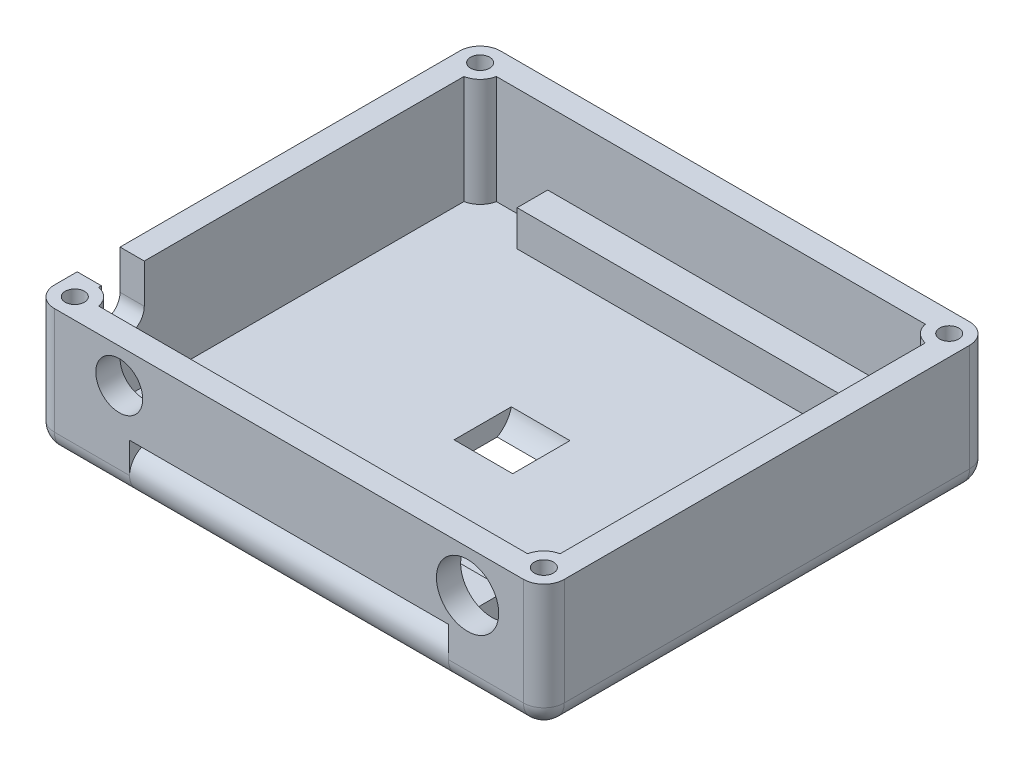
SolidWorks part; units mm, degrees
ref_plane "Front Plane" through (0, 0, 0) normal (0, 0, 1) x (1, 0, 0)
ref_plane "Top Plane" through (0, 0, 0) normal (0, 1, 0) x (1, 0, 0)
ref_plane "Right Plane" through (0, 0, 0) normal (1, 0, 0) x (0, 0, -1)
sketch "Sketch1" plane through (0, 0, 0) normal (0, 1, 0) x (1, 0, 0)
  line L1 (-20, -17.5) -> (20, -17.5)
  line L2 (-20, -17.5) -> (-20, 17.5)
  line L3 (-20, 17.5) -> (20, 17.5)
  line L4 (20, -17.5) -> (20, 17.5)
  line L5 (-20, -17.5) -> (20, 17.5) construction
  line L6 (-20, 17.5) -> (20, -17.5) construction
  point P0 (0, 0)
  dimension "D1" = 40
  dimension "D2" = 35
extrude "Boss-Extrude1" add sketch "Sketch1" along normal blind 10
sketch "Sketch3" plane through (0, 0, 17.5) normal (0, 0, 1) x (1, 0, 0)
  line L1 (-12.5, 0) -> (12.5, 0)
  line L2 (-12.5, 0) -> (-12.5, 4)
  line L3 (-12.5, 4) -> (12.5, 4)
  line L4 (12.5, 0) -> (12.5, 4)
  line L5 (-12.5, 0) -> (12.5, 4) construction
  line L6 (-12.5, 4) -> (12.5, 0) construction
  line L7 (-20, 0) -> (20, 0) construction
  point P0 (0, 2)
  dimension "D1" = 4
  dimension "D2" = 25
extrude "Cut-Extrude1" cut sketch "Sketch3" against normal blind 4
sketch "Sketch4" plane through (12.5, 0, 0) normal (-1, 0, 0) x (0, 0, 1)
  line L0 (17.5, 0) -> (17.5, 4) construction
  line L1 (13.5, 0) -> (17.5, 0) construction
  circle A0 centre (15.9, 1.6) radius 1.6
  dimension "D1" = 3.2
extrude "Boss-Extrude2" add sketch "Sketch4" along normal up to next
mirror "Mirror1" about plane through (0, 0, 0) normal (0, 0, 1) of "Cut-Extrude1", "Boss-Extrude2"
fillet "Fillet3" radius 1.6 12 edges at (0, 4, 13.5) (16.25, 0, 17.5) (-16.25, 0, 17.5) (0, 4, -13.5) (16.25, 0, -17.5) (-16.25, 0, -17.5) (20, 5, 17.5) (-20, 5, 17.5) (-20, 5, -17.5) (20, 5, -17.5) (20, 0, 0) (-20, 0, 0)
sketch "Sketch16" plane through (0, 10, 0) normal (0, 1, 0) x (1, 0, 0)
  line L24 (12.8, 15.6) -> (12.8, 13.2)
  line L25 (18.1, 15.6) -> (12.8, 15.6)
  line L26 (18.1, -15.6) -> (18.1, 15.6)
  line L27 (12.8, -15.6) -> (18.1, -15.6)
  line L28 (12.8, -13.2) -> (12.8, -15.6)
  line L29 (-12.8, -13.2) -> (12.8, -13.2)
  line L30 (-12.8, -15.6) -> (-12.8, -13.2)
  line L31 (-18.1, -15.6) -> (-12.8, -15.6)
  line L32 (-18.1, 15.6) -> (-18.1, -15.6)
  line L33 (-12.8, 15.6) -> (-18.1, 15.6)
  line L34 (-12.8, 13.2) -> (-12.8, 15.6)
  line L35 (12.8, 13.2) -> (-12.8, 13.2)
  line L36 (12.8, 15.6) -> (12.8, 13.2)
  line L37 (18.1, 15.6) -> (12.8, 15.6)
  line L38 (18.1, -15.6) -> (18.1, 15.6)
  line L39 (12.8, -15.6) -> (18.1, -15.6)
  line L40 (12.8, -13.2) -> (12.8, -15.6)
  line L41 (-12.8, -13.2) -> (12.8, -13.2)
  line L42 (-12.8, -15.6) -> (-12.8, -13.2)
  line L43 (-18.1, -15.6) -> (-12.8, -15.6)
  line L44 (-18.1, 15.6) -> (-18.1, -15.6)
  line L45 (-12.8, 15.6) -> (-18.1, 15.6)
  line L46 (-12.8, 13.2) -> (-12.8, 15.6)
  line L47 (12.8, 13.2) -> (-12.8, 13.2)
  dimension "D1" = 0.3
extrude "Cut-Extrude5" cut sketch "Sketch16" against normal offset from surface (8.5 mm away) 1.5 up to face at (0, 0, 0)
sketch "Sketch17" plane through (0, 10, 0) normal (0, 1, 0) x (1, 0, 0)
  line L8 (-18.1, -15.6) -> (18.1, -15.6)
  line L9 (18.1, -15.6) -> (18.1, 15.6)
  line L10 (18.1, 15.6) -> (-18.1, 15.6)
  line L11 (-18.1, 15.6) -> (-18.1, -15.6)
  line L12 (-18.1, -15.6) -> (18.1, -15.6)
  line L13 (18.1, -15.6) -> (18.1, 15.6)
  line L14 (18.1, 15.6) -> (-18.1, 15.6)
  line L15 (-18.1, 15.6) -> (-18.1, -15.6)
  dimension "D1" = 1.9
extrude "Cut-Extrude6" cut sketch "Sketch17" against normal offset from surface (5.7 mm away) 0.3 up to face at (0, 4, 16.3)
sketch "Sketch20" plane through (0, 10, 0) normal (0, 1, 0) x (1, 0, 0)
  line L0 (-5.5, 0) -> (5.5, 0) construction
  line L1 (0, -5.5) -> (0, 5.5) construction
  circle A0 centre (-18.4, -15.9) radius 1.6
  circle A1 centre (-18.4, 15.9) radius 1.6
  circle A2 centre (18.4, 15.9) radius 1.6
  circle A3 centre (18.4, -15.9) radius 1.6
extrude "Boss-Extrude3" add sketch "Sketch20" against normal up to next
hole_wizard "Ø1.5mm Dowel Hole1" positions "Sketch21" profile "Sketch22" hole size "Ø1.5" standard "ANSI Metric" end condition through all
sketch "Sketch21" plane through (0, 10, 0) normal (0, 1, 0) x (1, 0, 0)
  line L0 (18.4, 17.5) -> (-18.4, 17.5) construction
  line L1 (-20, 15.9) -> (-20, -15.9) construction
  point P0 (-18.4, 15.9)
  point P10 (18.4, 15.9)
  point P13 (18.4, -15.9)
  point P16 (-18.4, -15.9)
  dimension "D1" = 1.6
  dimension "D2" = 1.6
sketch "Sketch22" plane through (-18.4, 10, -15.9) normal (1, 0, 0) x (0, 0, 1)
  line L0 (0, 0) -> (0, 10)
  line L1 (0, 10) -> (0.75, 10)
  line L2 (0.75, 10) -> (0.75, 0)
  line L5 (0.75, 0) -> (0, 0)
  line L11 (0, -6.35) -> (0, 107.95) construction
  dimension "Thru Hole Dia." = 1.5
  dimension "Thru Hole Depth" = 10
sketch "Sketch23" plane through (0, 0, 0) normal (1, 0, 0) x (0, 0, -1)
  line L0 (-14.3284, 1.5) -> (14.3284, 1.5) construction
  circle A0 centre (0, 2) radius 2.3
  dimension "D1" = 0.5
extrude "Cut-Extrude8" cut sketch "Sketch23" against normal mid plane 4.6 contours A0
sketch "Sketch24" plane through (0, 0, 17.5) normal (0, 0, 1) x (1, 0, 0)
  circle A0 centre (-13.3117, 7.305) radius 1.8404
extrude "Cut-Extrude9" cut sketch "Sketch24" against normal up to next
sketch "Sketch26" plane through (0, 0, 17.5) normal (0, 0, 1) x (1, 0, 0)
  circle A0 centre (14.0146, 6.7161) radius 2.4438
extrude "Cut-Extrude11" cut sketch "Sketch26" against normal up to next
sketch "Sketch27" plane through (-20, 0, 0) normal (-1, 0, 0) x (0, 0, 1)
  line L10 (10.7492, 6.9264) -> (10.7492, 10)
  line L12 (14.1092, 10) -> (14.1092, 6.9264)
  line L13 (12.7578, 5.575) -> (12.1006, 5.575)
  line L14 (10.7492, 10) -> (14.1092, 10)
  line L15 (-15.9, 10) -> (15.9, 10) construction
  arc A2 (12.1006, 5.575) -> (10.7492, 6.9264) centre (12.1006, 6.9264) cw
  arc A3 (12.7578, 5.575) -> (14.1092, 6.9264) centre (12.7578, 6.9264) ccw
extrude "Cut-Extrude12" cut sketch "Sketch27" against normal up to next
